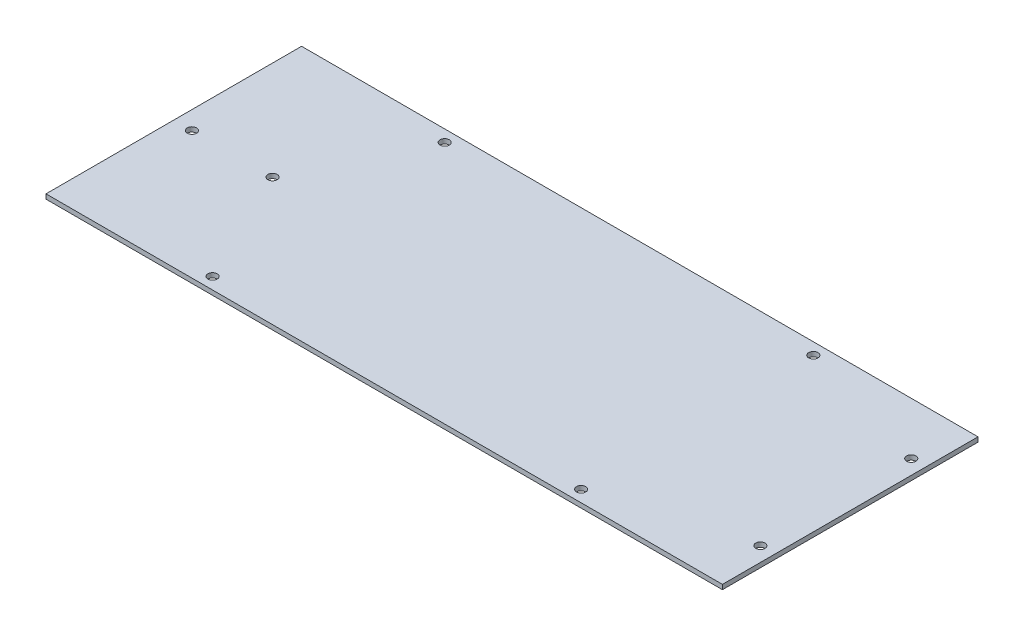
SolidWorks part; units mm, degrees
ref_plane "Front Plane" through (0, 0, 0) normal (0, 0, 1) x (1, 0, 0)
ref_plane "Top Plane" through (0, 0, 0) normal (0, 1, 0) x (1, 0, 0)
ref_plane "Right Plane" through (0, 0, 0) normal (1, 0, 0) x (0, 0, -1)
sketch "Sketch1" plane through (0, 0, 0) normal (0, 1, 0) x (1, 0, 0)
  line L10 (387.2115, -727.5276) -> (398.9404, -727.5276) construction
  line L13 (387.2115, -645.0276) -> (823.9284, -645.0276)
  line L21 (387.2115, -810.0276) -> (823.9284, -810.0276)
  line L24 (398.9404, -727.5276) -> (450.9912, -727.5276) construction
  line L26 (814.5673, -678.7596) -> (814.5673, -776.1876) construction
  line L36 (823.9284, -645.0276) -> (823.9284, -810.0276)
  line L38 (387.2115, -645.0276) -> (387.2115, -810.0276)
  circle A18 centre (814.5673, -678.7596) radius 3
  circle A20 centre (148.4698, -505.1001) radius 0.0028
  circle A21 centre (487.1593, -802.4576) radius 3
  circle A22 centre (487.1593, -652.5976) radius 3
  circle A23 centre (725.1593, -652.5976) radius 3
  circle A24 centre (725.1593, -802.4576) radius 3
  circle A25 centre (398.9404, -727.5276) radius 3
  circle A26 centre (450.9912, -727.5276) radius 3
  circle A27 centre (814.5673, -776.1876) radius 3
  point P4 (0, 0)
  point P5 (272.5206, -582.4819)
  dimension "D9" = 436.7169
  dimension "D3" = 165
  dimension "D6" = 7.57
  dimension "D23" = 6
  dimension "D4" = 7.57
  dimension "D5" = 7.57
  dimension "D7" = 11.7289
  dimension "D8" = 52.0508
  dimension "D14" = 33.732
extrude "Boss-Extrude1" add sketch "Sketch1" along normal blind 3 contours A25 L38 L21 L36 L13 A24 A23 A22 A21 A20 A18 A27 A26 region at (605.5467, 0, 727.5276)
